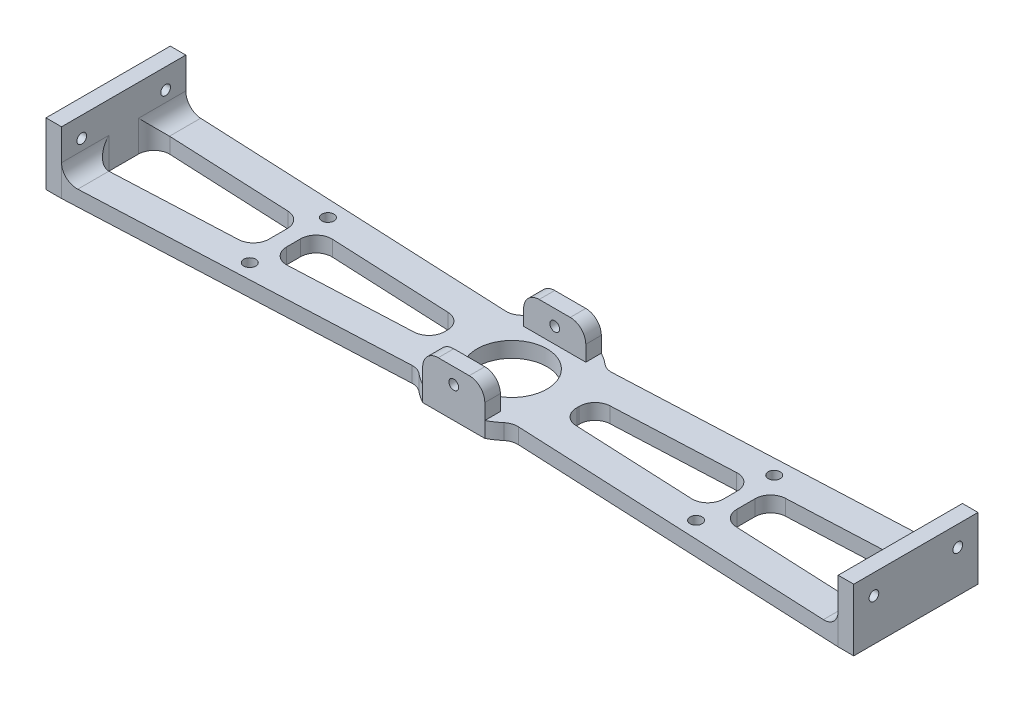
SolidWorks part; units mm, degrees
ref_plane "Front" through (0, 0, 0) normal (0, 0, 1) x (1, 0, 0)
ref_plane "Top" through (0, 0, 0) normal (0, 1, 0) x (1, 0, 0)
ref_plane "Right" through (0, 0, 0) normal (1, 0, 0) x (0, 0, -1)
sketch "Sketch1" plane through (0, 0, 0) normal (0, 1, 0) x (1, 0, 0)
  line L0 (-177.8, 0) -> (177.8, 0) construction
  line L1 (-190.5, 25.4) -> (-165.1, 25.4) construction
  line L2 (-190.5, 25.4) -> (-190.5, -25.4) construction
  line L3 (-190.5, -25.4) -> (-165.1, -25.4) construction
  line L4 (-165.1, 25.4) -> (-165.1, -25.4) construction
  line L5 (-190.5, 25.4) -> (-165.1, -25.4) construction
  line L6 (-190.5, -25.4) -> (-165.1, 25.4) construction
  line L7 (-158.75, 25.4) -> (-19.116, 19.05)
  line L8 (-158.75, 25.4) -> (-165.1, 25.4)
  line L9 (-158.75, 25.4) -> (-158.75, -25.4)
  line L10 (-158.75, -25.4) -> (-165.1, -25.4)
  line L11 (-165.1, 25.4) -> (-165.1, -25.4)
  line L12 (-158.75, 25.4) -> (-165.1, -25.4) construction
  line L13 (-158.75, -25.4) -> (-165.1, 25.4) construction
  line L14 (-158.75, -25.4) -> (-19.116, -19.05)
  line L15 (-158.75, 12.6869) -> (-26.1536, 6.6569)
  line L16 (-158.75, -12.6869) -> (-26.1536, -6.6569)
  line L17 (-159.3269, -12.7131) -> (-19.693, -6.3631) construction
  line L18 (-159.3269, 12.7131) -> (-19.693, 6.3631) construction
  line L19 (0, 0) -> (0, 26.9875) construction
  line L20 (92.4518, 9.6719) -> (92.4518, -9.6719) construction
  line L21 (-92.4518, 9.6719) -> (-92.4518, -9.6719) construction
  line L22 (-95.6268, 9.8163) -> (-95.6268, -9.8163)
  line L23 (-89.2768, 9.5275) -> (-89.2768, -9.5275)
  line L24 (-95.6268, 9.6719) -> (-95.6268, -9.6719) construction
  line L25 (-89.2768, 9.6719) -> (-89.2768, -9.6719) construction
  line L26 (158.75, -25.4) -> (165.1, 25.4) construction
  line L27 (158.75, 25.4) -> (165.1, -25.4) construction
  line L28 (190.5, -25.4) -> (165.1, 25.4) construction
  line L29 (190.5, 25.4) -> (165.1, -25.4) construction
  line L30 (165.1, 25.4) -> (165.1, -25.4) construction
  line L31 (190.5, -25.4) -> (165.1, -25.4) construction
  line L32 (190.5, 25.4) -> (190.5, -25.4) construction
  line L33 (190.5, 25.4) -> (165.1, 25.4) construction
  line L34 (89.2768, 9.5275) -> (89.2768, -9.5275)
  line L35 (95.6268, 9.8163) -> (95.6268, -9.8163)
  line L36 (158.75, -12.6869) -> (26.1536, -6.6569)
  line L37 (158.75, 12.6869) -> (26.1536, 6.6569)
  line L38 (158.75, -25.4) -> (19.116, -19.05)
  line L39 (165.1, 25.4) -> (165.1, -25.4)
  line L40 (158.75, -25.4) -> (165.1, -25.4)
  line L41 (158.75, 25.4) -> (158.75, -25.4)
  line L42 (158.75, 25.4) -> (165.1, 25.4)
  line L43 (158.75, 25.4) -> (19.116, 19.05)
  line L44 (-23.7036, 12.9021) -> (-158.75, 19.0434) construction
  line L45 (-23.7036, -12.9021) -> (-158.75, -19.0434) construction
  line L46 (23.7036, -12.9021) -> (158.75, -19.0434) construction
  line L47 (23.7036, 12.9021) -> (158.75, 19.0434) construction
  line L48 (-12.7, -23.8125) -> (-12.7, -25.4)
  line L49 (-12.7, 23.8125) -> (12.7, 23.8125)
  line L50 (-12.7, 23.8125) -> (-12.7, 25.4)
  line L51 (-12.7, 25.4) -> (12.7, 25.4)
  line L52 (12.7, 23.8125) -> (12.7, 25.4)
  line L53 (-12.7, -23.8125) -> (12.7, -23.8125)
  line L54 (12.7, -23.8125) -> (12.7, -25.4)
  line L55 (-12.7, -25.4) -> (12.7, -25.4)
  circle A0 centre (0, 0) radius 14.2875
  circle A1 centre (0, 0) radius 26.9875
  point P5 (-177.8, 0)
  point P11 (-161.925, 0)
  point P41 (161.925, 0)
  point P69 (9.2443, 25.3549)
  dimension "D1" = 28.575
  dimension "D3" = 50.8
  dimension "D4" = 25.4
  dimension "D5" = 38.1
  dimension "D10" = 6.35
  dimension "D11" = 355.6
  dimension "D12" = 6.35
  dimension "D13" = 25.4
  dimension "D2" = 12.7
  dimension "D6" = 12.7
  dimension "D7" = 12.7
  dimension "D8" = 3.175
  dimension "D9" = 3.175
extrude "Boss-Extrude1" add sketch "Sketch1" along normal mid plane 6.35 contours A1 L7 L9 L15 | A1 L16 L9 L14 | A1 A0 | A1 L38 L41 L36 | A1 L37 L41 L43 | L23 L15 L22 L16 | L8 L11 L10 L9 | L42 L41 L40 L39 | L35 L37 L34 L36 region at (-161.925, 0, 0) region at (-91.0365, 0, -16.0182) region at (-15.6562, 0, -21.092) region at (-91.0365, 0, 16.0182) region at (-92.4676, 0, 0) region at (91.0365, 0, -16.0182) region at (161.925, 0, 0) region at (92.4676, 0, 0) region at (91.0365, 0, 16.0182)
sketch "Sketch2" plane through (0, 3.175, 0) normal (0, 1, 0) x (1, 0, 0)
  line L1 (-165.1, 25.4) -> (-158.75, 25.4)
  line L2 (-165.1, 25.4) -> (-165.1, -25.4)
  line L3 (-165.1, -25.4) -> (-158.75, -25.4)
  line L4 (-158.75, 25.4) -> (-158.75, -25.4)
  line L5 (165.1, 25.4) -> (158.75, 25.4)
  line L6 (165.1, 25.4) -> (165.1, -25.4)
  line L7 (165.1, -25.4) -> (158.75, -25.4)
  line L8 (158.75, 25.4) -> (158.75, -25.4)
extrude "Boss-Extrude2" add sketch "Sketch2" along normal blind 19.05
sketch "Sketch7" plane through (0, 3.175, 0) normal (0, 1, 0) x (1, 0, 0)
  line L0 (-12.7, 23.8125) -> (12.7, 23.8125) construction
  line L1 (-12.7, 23.8125) -> (12.7, 23.8125)
  line L2 (-12.7, 23.8125) -> (-12.7, 17.4625)
  line L3 (-12.7, 17.4625) -> (12.7, 17.4625)
  line L4 (12.7, 23.8125) -> (12.7, 17.4625)
  line L5 (0, 0) -> (-25.5645, 0) construction
  line L6 (-12.7, -23.8125) -> (12.7, -23.8125)
  line L7 (12.7, -23.8125) -> (12.7, -17.4625)
  line L8 (-12.7, -17.4625) -> (12.7, -17.4625)
  line L9 (-12.7, -23.8125) -> (-12.7, -17.4625)
  arc A0 (-12.7, 23.8125) -> (-19.116, 19.05) centre (0, 0) ccw construction
  dimension "D1" = 6.35
extrude "Boss-Extrude3" add sketch "Sketch7" along normal blind 12.7
fillet "Fillet1" radius 6.35 28 edges at (-19.116, 0, -19.05) (19.116, 0, -19.05) (19.116, 0, 19.05) (-19.116, 0, 19.05) (158.75, 3.175, 19.0434) (158.75, 3.175, -19.0434) (-158.75, 3.175, -19.0434) (-158.75, 3.175, 19.0434) (-158.75, 0, -12.6869) (-95.6268, 0, -9.8163) (-95.6268, 0, 9.8163) (-158.75, 0, 12.6869) (158.75, 0, -12.6869) (95.6268, 0, 9.8163) (95.6268, 0, -9.8163) (158.75, 0, 12.6869) (-26.1536, 0, -6.6569) (-89.2768, 0, -9.5275) (-89.2768, 0, 9.5275) (-26.1536, 0, 6.6569) (26.1536, 0, -6.6569) (26.1536, 0, 6.6569) (89.2768, 0, -9.5275) (89.2768, 0, 9.5275) (12.7, 15.875, 20.6375) (-12.7, 15.875, 20.6375) (12.7, 15.875, -20.6375) (-12.7, 15.875, -20.6375)
hole_wizard "#10 (0.1935) Diameter Hole1" positions "Sketch3" profile "Sketch4" hole size "#10" standard "ANSI Inch" end condition through all
sketch "Sketch3" plane through (0, 3.175, 0) normal (0, 1, 0) x (1, 0, 0)
  line L0 (-23.7036, 12.9021) -> (-158.75, 19.0434) construction
  line L1 (-23.7036, -12.9021) -> (-158.75, -19.0434) construction
  line L2 (23.7036, 12.9021) -> (158.75, 19.0434) construction
  line L3 (23.7036, -12.9021) -> (158.75, -19.0434) construction
  point P0 (-91.2268, 15.9728)
  point P6 (-91.2268, -15.9728)
  point P11 (91.2268, 15.9728)
  point P13 (91.2268, -15.9728)
  point P15 (0, 0)
  point P18 (0, 0)
sketch "Sketch4" plane through (-91.2268, 3.175, -15.9728) normal (1, 0, 0) x (0, 0, 1)
  line L0 (0, 0) -> (0, 6.35)
  line L1 (0, 6.35) -> (2.4574, 6.35)
  line L2 (2.4574, 6.35) -> (2.4574, 0)
  line L5 (2.4574, 0) -> (0, 0)
  line L11 (0, -6.35) -> (0, 107.95) construction
  dimension "Thru Hole Dia." = 4.9149
  dimension "Thru Hole Depth" = 6.35
hole_wizard "5/32 (0.15625) Diameter Hole1" positions "Sketch5" profile "Sketch6" hole size "5/32" standard "ANSI Inch" end condition through all
sketch "Sketch5" plane through (-158.75, 0, 0) normal (1, 0, 0) x (0, 0, -1)
  line L0 (25.4, 13.97) -> (-25.4, 13.97) construction
  line L1 (25.4, 22.225) -> (25.4, 9.525) construction
  line L2 (-25.4, 22.225) -> (-25.4, 9.525) construction
  line L4 (-25.4, 22.225) -> (25.4, 22.225) construction
  line L5 (0, 13.97) -> (0, 22.225) construction
  point P0 (17.145, 13.97)
  point P16 (-17.145, 13.97)
  dimension "D1" = 8.255
  dimension "D2" = 8.255
sketch "Sketch6" plane through (-158.75, 13.97, -17.145) normal (0, 1, 0) x (0, 0, -1)
  line L0 (0, 0) -> (0, 6.35)
  line L1 (0, 6.35) -> (1.9844, 6.35)
  line L2 (1.9844, 6.35) -> (1.9844, 0)
  line L5 (1.9844, 0) -> (0, 0)
  line L11 (0, -6.35) -> (0, 107.95) construction
  dimension "Thru Hole Dia." = 3.9688
  dimension "Thru Hole Depth" = 6.35
mirror "Mirror1" about plane through (0, 0, 0) normal (1, 0, 0) of "5/32 (0.15625) Diameter Hole1"
hole_wizard "5/32 (0.15625) Diameter Hole2" positions "Sketch8" profile "Sketch9" hole size "5/32" standard "ANSI Inch" end condition through all
sketch "Sketch8" plane through (0, 0, -23.8125) normal (0, 0, -1) x (-1, 0, 0)
  line L0 (0, -3.175) -> (0, 9.525) construction
  line L1 (12.7, -3.175) -> (-12.7, -3.175) construction
  point P0 (0, 9.525)
  point P7 (0, 7.3336)
  dimension "D1" = 12.7
sketch "Sketch9" plane through (0, 9.525, -23.8125) normal (1, 0, 0) x (0, 1, 0)
  line L0 (0, 0) -> (0, 49.2125)
  line L1 (0, 49.2125) -> (1.9844, 49.2125)
  line L2 (1.9844, 49.2125) -> (1.9844, 0)
  line L5 (1.9844, 0) -> (0, 0)
  line L11 (0, -6.35) -> (0, 107.95) construction
  dimension "Thru Hole Dia." = 3.9688
  dimension "Thru Hole Depth" = 49.2125
